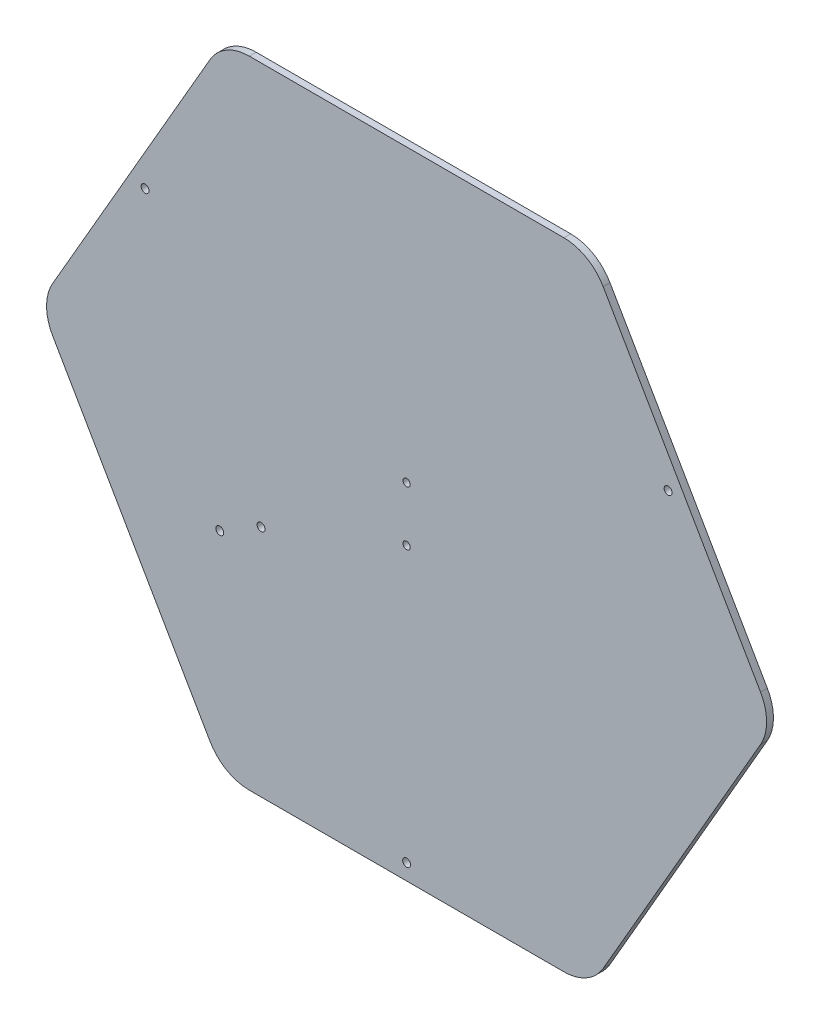
SolidWorks part; units mm, degrees
ref_plane "Alzado" through (0, 0, 0) normal (0, 0, 1) x (1, 0, 0)
ref_plane "Planta" through (0, 0, 0) normal (0, 1, 0) x (1, 0, 0)
ref_plane "Vista lateral" through (0, 0, 0) normal (1, 0, 0) x (0, 0, -1)
sketch "Croquis1" plane through (0, 0, 0) normal (0, 0, 1) x (1, 0, 0)
  line L0 (11.25, 96) -> (-11.25, 84) construction
  line L1 (-11.25, 96) -> (11.25, 96)
  line L2 (-11.25, 96) -> (-11.25, 84)
  line L3 (-11.25, 84) -> (11.25, 84)
  line L4 (11.25, 96) -> (11.25, 84)
  line L5 (-11.25, 96) -> (11.25, 84) construction
  line L6 (88.7634, -38.2572) -> (78.3711, -32.2572)
  line L7 (88.7634, -38.2572) -> (77.5134, -57.7428)
  line L8 (77.5134, -57.7428) -> (67.1211, -51.7428)
  line L9 (78.3711, -32.2572) -> (67.1211, -51.7428)
  line L10 (-77.5134, -57.7428) -> (-67.1211, -51.7428)
  line L11 (-77.5134, -57.7428) -> (-88.7634, -38.2572)
  line L12 (-88.7634, -38.2572) -> (-78.3711, -32.2572)
  line L13 (-67.1211, -51.7428) -> (-78.3711, -32.2572)
  line L14 (0, -0.7536) -> (0, 0) construction
  line L15 (0, 0) -> (0, 17.5) construction
  line L17 (-80.829, -140) -> (80.829, -140)
  line L18 (80.829, -140) -> (161.6581, 0)
  line L19 (161.6581, 0) -> (80.829, 140)
  line L20 (80.829, 140) -> (-80.829, 140)
  line L21 (-80.829, 140) -> (-161.6581, 0)
  line L22 (-161.6581, 0) -> (-80.829, -140)
  circle A0 centre (0, 0) radius 150
  circle A1 centre (0, 0) radius 10.8
  circle A2 centre (0, 0) radius 90 construction
  circle A3 centre (0, 90) radius 40 construction
  circle A4 centre (77.9423, -45) radius 40 construction
  circle A5 centre (-77.9423, -45) radius 40 construction
  circle A6 centre (0, 0) radius 17.5 construction
  circle A7 centre (0, 17.5) radius 2.6
  circle A8 centre (0, 0) radius 140 construction
  circle A9 centre (15.1554, -8.75) radius 2.6
  circle A10 centre (-15.1554, -8.75) radius 2.6
  point P11 (0, 90)
  point P18 (0, 0)
  point P28 (0, 0)
  point P39 (0, 0)
  dimension "D1" = 300
  dimension "D2" = 21.6
  dimension "D3" = 180
  dimension "D4" = 80
  dimension "D9" = 5.2
  dimension "D10" = 3
  dimension "D11" = 50
  dimension "D5" = 12
  dimension "D6" = 22.5
  dimension "D7" = 3
  dimension "D8" = 3
extrude "Saliente-Extruir1" add sketch "Croquis1" along normal blind 3 contours L19 A0 L20 L21 L22 L17 L18 A10 A9 A7 A1 L1 L4 L3 L2 L9 L6 L7 L8 L13 L10 L11 L12 | A0 L20 L21 | A0 L19 L20 | A0 L18 L19 | A0 L17 L18 | A0 L22 L17 | A0 L21 L22 | A10 | A1 | A9 | A7 | L11 L12 L13 L10 | L9 L8 L7 L6 | L3 L4 L1 L2 region at (-76.7492, -132.9335, 0) region at (-72.9482, -126.3499, 0) region at (76.7492, -132.9335, 0) region at (-153.4984, 0, 0) region at (153.4984, 0, 0) region at (-76.7492, 132.9335, 0) region at (76.7492, 132.9335, 0) region at (0, 0, 0) region at (0, 17.5, 0) region at (15.1554, -8.75, 0) region at (-15.1554, -8.75, 0)
fillet "Redondeo1" radius 20 6 edges at (80.829, 140, 1.5) (-80.829, 140, 1.5) (-161.6581, 0, 1.5) (-80.829, -140, 1.5) (80.829, -140, 1.5) (161.6581, 0, 1.5)
sketch "Croquis2" plane through (0, 0, 0) normal (0, 0, -1) x (1, 0, 0)
  circle A0 centre (0, 133) radius 1.75
  circle A1 centre (115.1814, -66.5) radius 1.75
  circle A2 centre (-115.1814, -66.5) radius 1.75
  point P9 (0, 0)
  dimension "D1" = 3
extrude "Cortar-Extruir1" cut sketch "Croquis2" against normal through all
sketch "Croquis3" plane through (0, 0, 74.15) normal (0, 0, 1) x (1, 0, 0)
  circle A0 centre (-64.0939, -37.0046) radius 1.75
  circle A1 centre (-82.2805, -47.5046) radius 1.75
  dimension "D1" = 3.5
extrude "Cortar-Extruir2" cut sketch "Croquis3" against normal through all
sketch "Croquis4" plane through (0, 0, 74.15) normal (0, 0, 1) x (1, 0, 0)
  circle A0 centre (0, 12) radius 1.6
  circle A1 centre (0, -12) radius 1.6
  dimension "D1" = 3.2
  dimension "D2" = 3.2
extrude "Cortar-Extruir3" cut sketch "Croquis4" against normal through all
